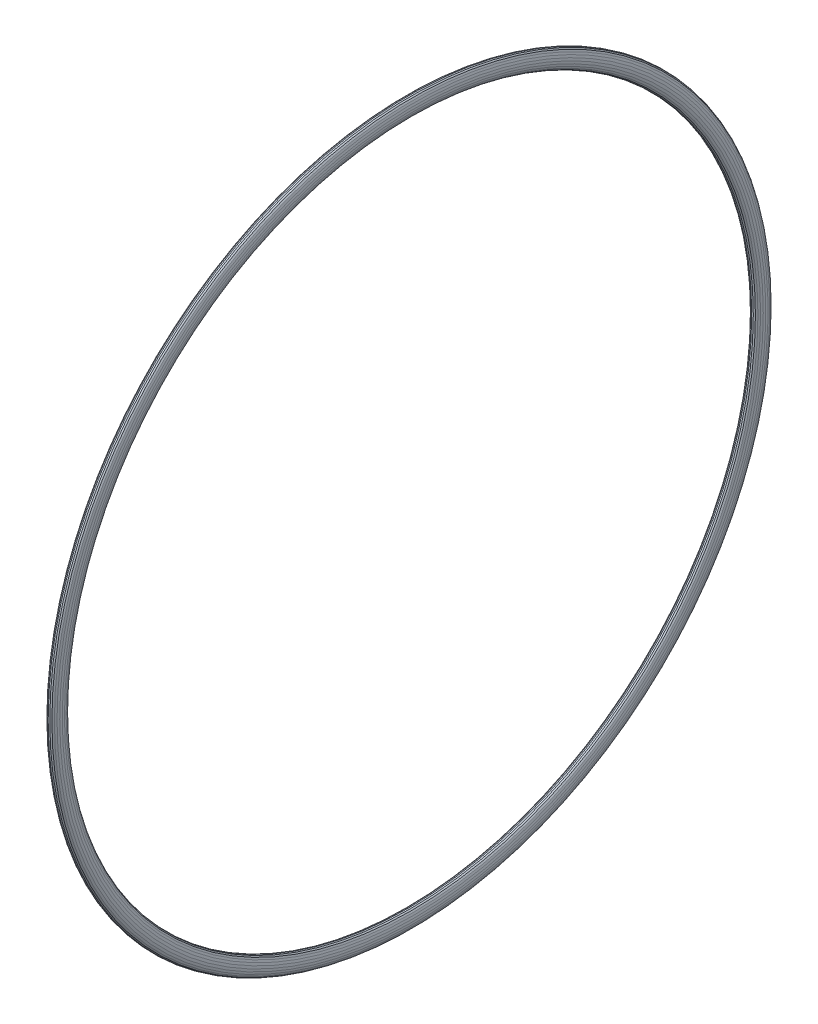
SolidWorks part; units mm, degrees
ref_plane "Front Plane" through (0, 0, 0) normal (0, 0, 1) x (1, 0, 0)
ref_plane "Top Plane" through (0, 0, 0) normal (0, 1, 0) x (1, 0, 0)
ref_plane "Right Plane" through (0, 0, 0) normal (1, 0, 0) x (0, 0, -1)
sketch "O_Ring_Outer Sketch" plane through (0, 0, 0) normal (0, 0, 1) x (1, 0, 0)
  line L0 (-1000, 0) -> (1000, 0) construction
  line L1 (-1.955, 68.28) -> (-1.9218, 68.7355)
  line L2 (-1.9218, 68.7355) -> (-1.8244, 69.1601)
  line L3 (-1.8244, 69.1601) -> (-1.6694, 69.5246)
  line L4 (-1.6694, 69.5246) -> (-1.4675, 69.8043)
  line L5 (-1.4675, 69.8043) -> (-1.2323, 69.9801)
  line L6 (-1.2323, 69.9801) -> (-0.98, 70.0401)
  line L7 (-0.98, 70.0401) -> (-0.7277, 69.9801)
  line L8 (-0.7277, 69.9801) -> (-0.4925, 69.8043)
  line L9 (-0.4925, 69.8043) -> (-0.2906, 69.5246)
  line L10 (-0.2906, 69.5246) -> (-0.1356, 69.1601)
  line L11 (-0.1356, 69.1601) -> (-0.0382, 68.7355)
  line L12 (-0.0382, 68.7355) -> (-0.005, 68.28)
  line L13 (-0.005, 68.28) -> (-0.0382, 67.8245)
  line L14 (-0.0382, 67.8245) -> (-0.1356, 67.3999)
  line L15 (-0.1356, 67.3999) -> (-0.2906, 67.0354)
  line L16 (-0.2906, 67.0354) -> (-0.4925, 66.7557)
  line L17 (-0.4925, 66.7557) -> (-0.7277, 66.5799)
  line L18 (-0.7277, 66.5799) -> (-0.98, 66.5199)
  line L19 (-0.98, 66.5199) -> (-1.2323, 66.5799)
  line L20 (-1.2323, 66.5799) -> (-1.4675, 66.7557)
  line L21 (-1.4675, 66.7557) -> (-1.6694, 67.0354)
  line L22 (-1.6694, 67.0354) -> (-1.8244, 67.3999)
  line L23 (-1.8244, 67.3999) -> (-1.9218, 67.8245)
  line L24 (-1.9218, 67.8245) -> (-1.955, 68.28)
revolve "O_Ring_Outer" add sketch "O_Ring_Outer Sketch" angle 360 about L0
ref_axis "Engine Axis" through (0.0925, 0, 0) along (-1, 0, 0)
